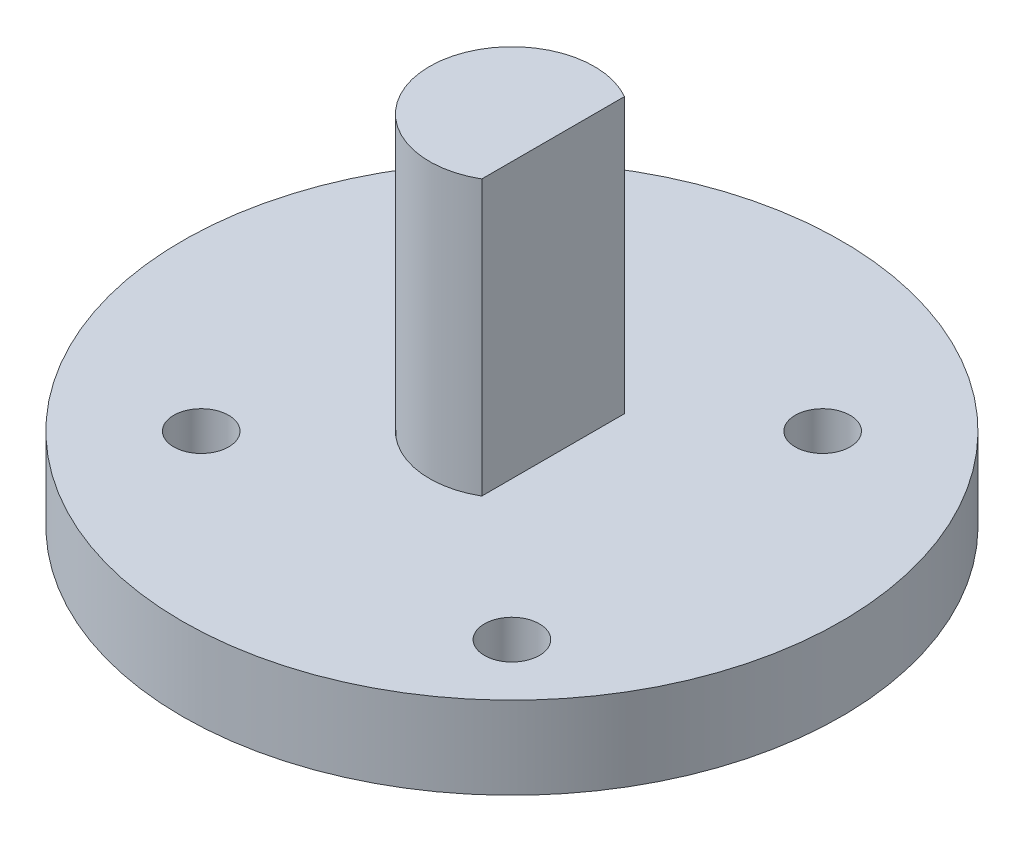
SolidWorks part; units mm, degrees
ref_plane "Alzado" through (0, 0, 0) normal (0, 0, 1) x (1, 0, 0)
ref_plane "Planta" through (0, 0, 0) normal (0, 1, 0) x (1, 0, 0)
ref_plane "Vista lateral" through (0, 0, 0) normal (1, 0, 0) x (0, 0, -1)
sketch "Croquis1" plane through (0, 0, 0) normal (0, 1, 0) x (1, 0, 0)
  line L0 (0, 0) -> (-6.6149, 6.6149) construction
  line L1 (-6.6149, 6.6149) -> (7.3418, -7.3418) construction
  line L2 (0, 0) -> (-7.8255, -7.8255) construction
  line L3 (-7.8255, -7.8255) -> (6.0905, 6.0905) construction
  circle A0 centre (0, 0) radius 12
  circle A1 centre (-6.5761, 6.5761) radius 1
  circle A6 centre (0, 0) radius 3
  circle A7 centre (5.6569, 5.6569) radius 1
  circle A8 centre (6.5761, -6.5761) radius 1
  circle A9 centre (-5.6569, -5.6569) radius 1
  circle A10 centre (0, 0) radius 9.3 construction
  circle A11 centre (0, 0) radius 8 construction
  point P10 (0, 0)
  point P11 (0, 0)
  point P12 (0, 0)
  point P13 (0, 0)
  point P14 (-1.6569, -4)
  point P23 (0, 0)
  point P24 (0, 0)
  point P25 (0, 0)
  point P26 (0, 0)
  point P27 (0, 0)
  point P28 (0, 0)
  dimension "D1" = 24
  dimension "D2" = 2
  dimension "D5" = 18.6
  dimension "D6" = 6
  dimension "D8" = 16
  dimension "D7" = 45
extrude "Saliente-Extruir1" add sketch "Croquis1" along normal blind 3 contours A0 A6 A1 | A6 region at (-11.6606, 0, 0) region at (0, 0, 0)
extrude "Saliente-Extruir2" add sketch "Croquis1<3>" along normal blind 10 from surface contours A6 starting at face at (-5.6569, 3, 6.6569)
sketch "Croquis1<3>" plane through (0, 0, 0) normal (0, 1, 0) x (1, 0, 0) same geometry as "Croquis1"
sketch "Croquis2" plane through (0, 13, 0) normal (0, 1, 0) x (1, 0, 0)
  line L0 (1.5, 2.5981) -> (1.5, -2.5981)
  circle A0 centre (0, 0) radius 3 construction
  arc A1 (1.5, -2.5981) -> (1.5, 2.5981) centre (0, 0) ccw
  dimension "D1" = 1.5
extrude "Cortar-Extruir1" cut sketch "Croquis2" against normal up to surface (10 mm away) up to face at (0, 3, 3)
